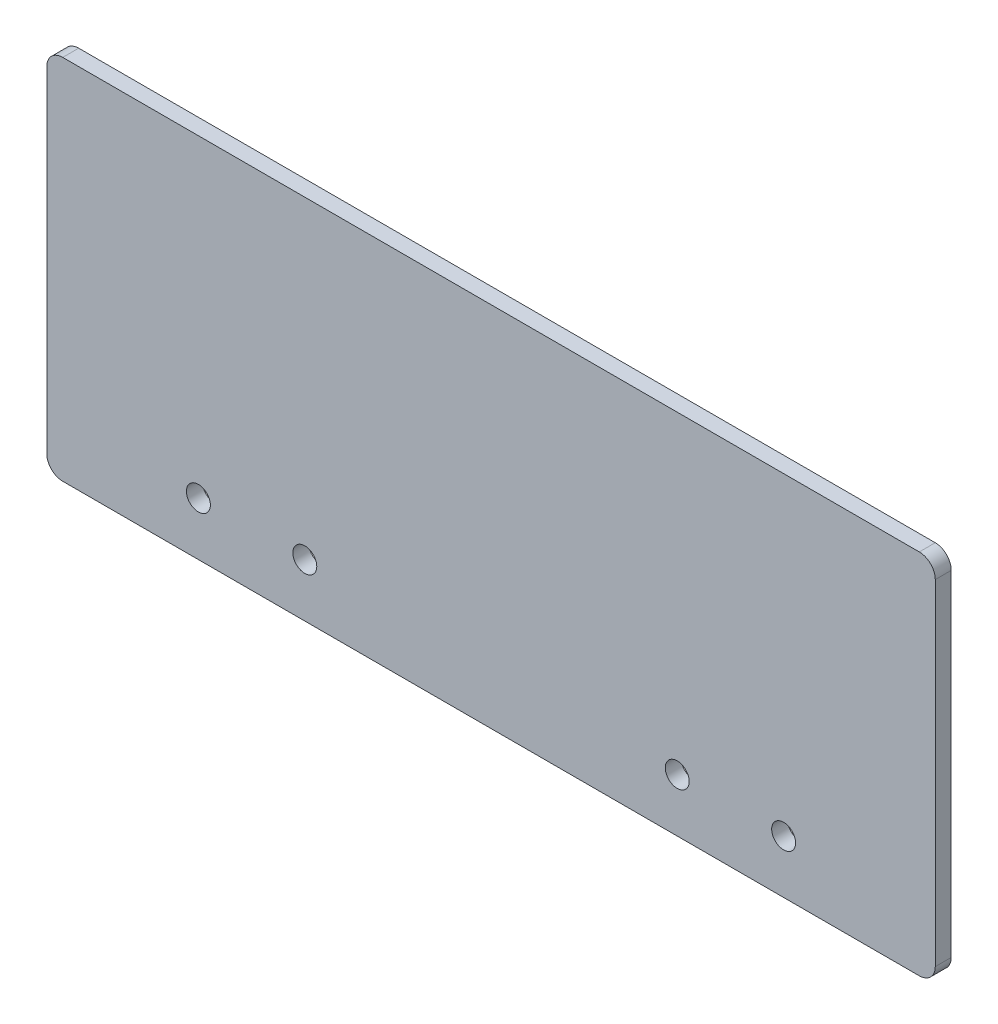
SolidWorks part; units mm, degrees
ref_plane "Front" through (0, 0, 0) normal (0, 0, 1) x (1, 0, 0)
ref_plane "Top" through (0, 0, 0) normal (0, 1, 0) x (1, 0, 0)
ref_plane "Right" through (0, 0, 0) normal (1, 0, 0) x (0, 0, -1)
sketch "Esquisse1" plane through (0, 0, 0) normal (0, 0, 1) x (1, 0, 0)
  line L1 (0, 0) -> (167, 0)
  line L2 (0, 0) -> (0, 69)
  line L3 (0, 69) -> (167, 69)
  line L4 (167, 0) -> (167, 69)
  dimension "D1" = 167
  dimension "D2" = 69
extrude "Boss.-Extru.1" add sketch "Esquisse1" along normal blind 3
fillet "Congé1" radius 3 4 edges at (167, 0, 1.5) (167, 69, 1.5) (0, 69, 1.5) (0, 0, 1.5)
sketch "Esquisse2" plane through (0, 0, 3) normal (0, 0, 1) x (1, 0, 0)
  line L0 (83.5, 69) -> (83.5, 0) construction
  line L1 (164, 69) -> (3, 69) construction
  line L2 (3, 0) -> (164, 0) construction
  line L3 (28.5, 10) -> (48.5, 10) construction
  line L4 (138.5, 10) -> (118.5, 10) construction
  circle A0 centre (28.5, 10) radius 2.25
  circle A1 centre (48.5, 10) radius 2.25
  circle A2 centre (118.5, 10) radius 2.25
  circle A3 centre (138.5, 10) radius 2.25
  dimension "D1" = 110
  dimension "D2" = 4.5
  dimension "D3" = 10
  dimension "D4" = 20
extrude "Enlèv. mat.-Extru.1" cut sketch "Esquisse2" against normal through all both and the other way through all
